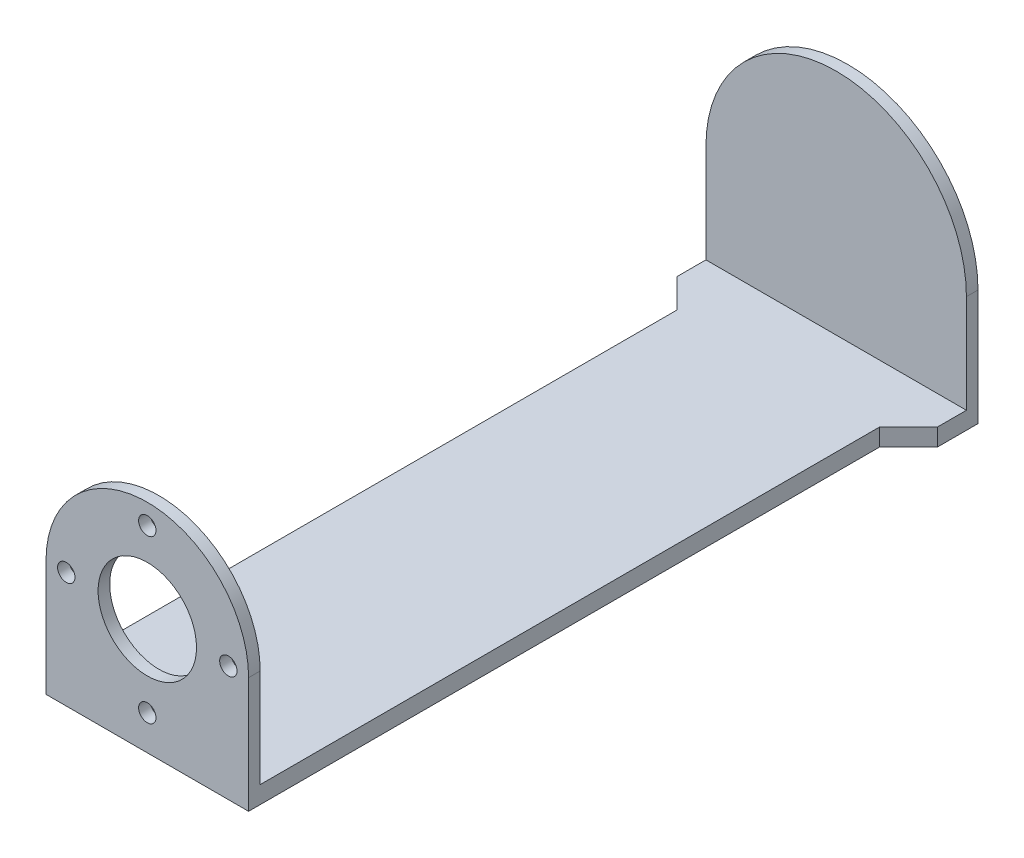
SolidWorks part; units mm, degrees
ref_plane "Front Plane" through (0, 0, 0) normal (0, 0, 1) x (1, 0, 0)
ref_plane "Top Plane" through (0, 0, 0) normal (0, 1, 0) x (1, 0, 0)
ref_plane "Right Plane" through (0, 0, 0) normal (1, 0, 0) x (0, 0, -1)
sketch "Sketch1" plane through (0, 0, 0) normal (0, 0, 1) x (1, 0, 0)
  line L0 (-17.5, 0) -> (-17.5, -20)
  line L1 (-17.5, -20) -> (17.5, -20)
  line L2 (17.5, -20) -> (17.5, 0)
  arc A0 (17.5, 0) -> (-17.5, 0) centre (0, 0) ccw
  circle A1 centre (0, 0) radius 14 construction
  circle A2 centre (0, 14) radius 1.5
  circle A4 centre (14, 0) radius 1.5
  circle A5 centre (0, -14) radius 1.5
  circle A6 centre (-14, 0) radius 1.5
  circle A7 centre (0, 0) radius 8.5
  point P18 (0, 0)
  dimension "D1" = 35
  dimension "D4" = 28
  dimension "D5" = 3
  dimension "D6" = 17
  dimension "D3" = 20
  dimension "D2" = 4
extrude "Boss-Extrude1" add sketch "Sketch1" along normal blind 2
sketch "Sketch2" plane through (0, 0, 0) normal (0, 0, -1) x (-1, 0, 0)
  line L0 (17.5, -20) -> (-17.5, -20)
  line L1 (-17.5, -20) -> (-17.5, -17)
  line L2 (-17.5, -20) -> (-17.5, 0) construction
  line L3 (-17.5, -17) -> (17.5, -17)
  line L4 (17.5, 0) -> (17.5, -20) construction
  line L5 (17.5, -17) -> (17.5, -20)
  dimension "D1" = 3
extrude "Boss-Extrude2" add sketch "Sketch2" along normal up to surface (117 mm away)
sketch "Sketch3" plane through (0, 0, -117) normal (0, 0, -1) x (-1, 0, 0)
  line L0 (-17.5, -20) -> (-22.5, -20)
  line L1 (-22.5, -20) -> (-22.5, 0)
  line L2 (17.5, -20) -> (22.5, -20)
  line L3 (22.5, -20) -> (22.5, 0)
  line L8 (17.5, -17) -> (-17.5, -17)
  line L9 (-17.5, -17) -> (-17.5, -20)
  line L10 (-17.5, -20) -> (17.5, -20)
  line L11 (17.5, -20) -> (17.5, -17)
  line L14 (-17.5, -20) -> (17.5, -20)
  arc A0 (22.5, 0) -> (-22.5, 0) centre (0, 0) ccw
  dimension "D1" = 5
  dimension "D2" = 0
extrude "Boss-Extrude3" add sketch "Sketch3" along normal blind 2
chamfer "Chamfer1" distance 10 angle 45 2 edges at (17.5, -18.5, -117) (-17.5, -18.5, -117)
